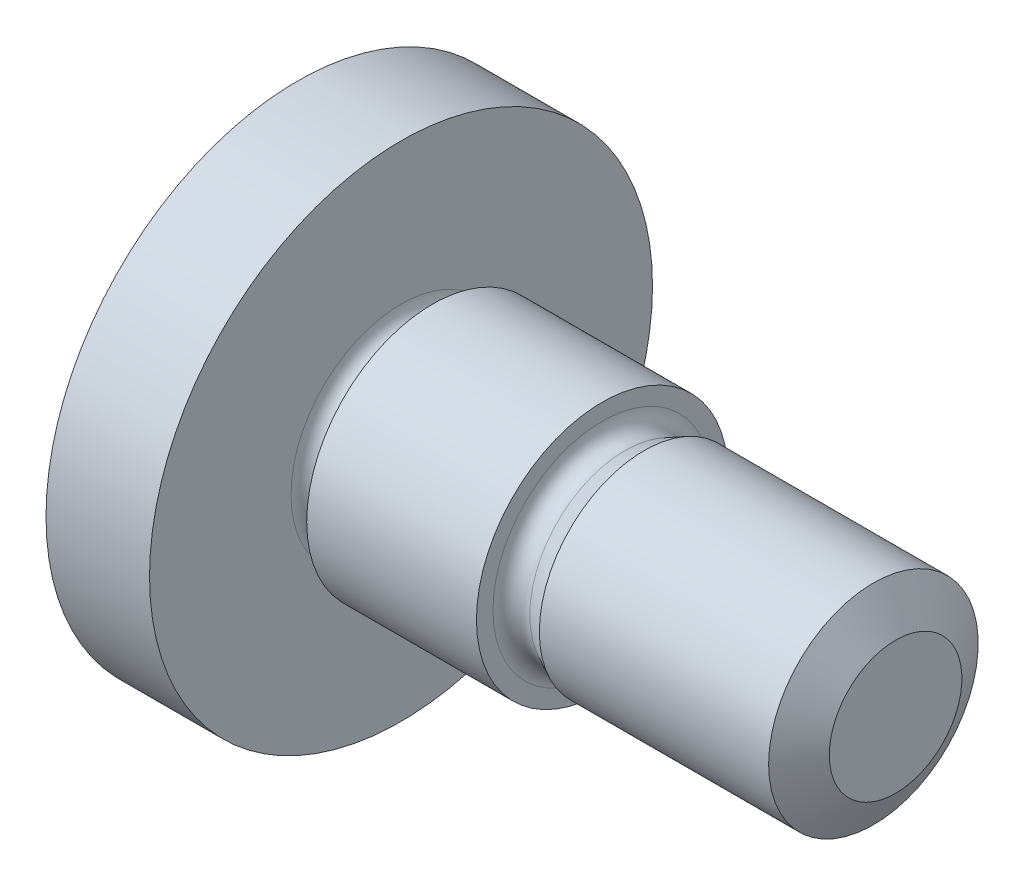
SolidWorks part; units mm, degrees
ref_plane "Płaszczyzna przednia" through (0, 0, 0) normal (0, 0, 1) x (1, 0, 0)
ref_plane "Płaszczyzna górna" through (0, 0, 0) normal (0, 1, 0) x (1, 0, 0)
ref_plane "Płaszczyzna prawa" through (0, 0, 0) normal (1, 0, 0) x (0, 0, -1)
sketch "Szkic1" plane through (0, 0, 0) normal (0, 0, 1) x (1, 0, 0)
  line L0 (0, 0) -> (0, 5.082)
  line L1 (0, 5.082) -> (0.53, 6)
  line L2 (0.53, 6) -> (3, 6)
  line L3 (3, 6) -> (3, 2.25)
  line L4 (3, 2.25) -> (3.75, 2.25)
  line L5 (3.75, 2.25) -> (3.75, 3)
  line L6 (3.75, 3) -> (7.8, 3)
  line L7 (7.8, 3) -> (7.8, 2)
  line L8 (7.8, 2) -> (8.8, 2.5)
  line L9 (8.8, 2.5) -> (14.27, 2.5)
  line L10 (14.27, 2.5) -> (14.8, 1.582)
  line L11 (14.8, 1.582) -> (14.8, 0)
  line L12 (0, 0) -> (14.8, 0)
  dimension "D2" = 6
  dimension "D3" = 3
  dimension "D4" = 3
  dimension "D5" = 2.5
  dimension "D6" = 7
  dimension "D7" = 150
  dimension "D8" = 0.53
  dimension "D9" = 0.75
  dimension "D10" = 0.75
  dimension "D11" = 1
  dimension "D12" = 150
  dimension "D13" = 0.53
  dimension "D14" = 1
  dimension "D15" = 4.8
revolve "Obrót1" add sketch "Szkic1" angle 360 about L12
sketch "Szkic2" plane through (0, 0, 0) normal (-1, 0, 0) x (0, 0, 1)
  line L1 (0, -1.7321) -> (1.5, -0.866)
  line L2 (1.5, -0.866) -> (1.5, 0.866)
  line L3 (1.5, 0.866) -> (0, 1.7321)
  line L4 (0, 1.7321) -> (-1.5, 0.866)
  line L5 (-1.5, 0.866) -> (-1.5, -0.866)
  line L6 (-1.5, -0.866) -> (0, -1.7321)
  circle A0 centre (0, 0) radius 1.5 construction
  dimension "D1" = 3
extrude "Wytnij-wyciągnięcie1" cut sketch "Szkic2" against normal blind 3
sketch "Szkic3" plane through (0, 0, 0) normal (0, 0, 1) x (1, 0, 0)
  line L0 (-0.9028, 0) -> (4.8749, 0) construction
  line L3 (3, 0) -> (3, 1.7321)
  line L4 (3, 1.7321) -> (3.8077, 0)
  line L8 (3.8077, 0) -> (3, 0)
  dimension "D2" = 25
  dimension "D4" = 5.7777
  dimension "D5" = 3
  dimension "D6" = 0.9028
revolve "Wycięcie-obrót1" cut sketch "Szkic3" angle 360 about L0
fillet "Zaokrąglenie2" radius 0.375 3 edges at (7.8, 0, 2) (3, 0, 2.25) (3.75, 0, 2.25)
